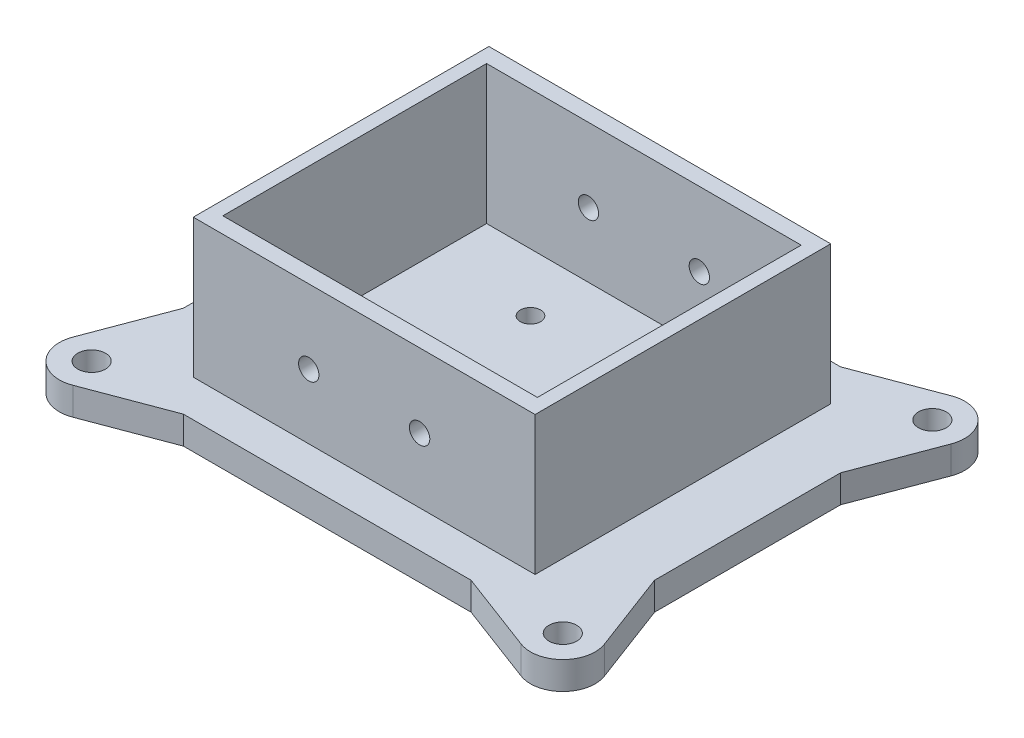
SolidWorks part; units mm, degrees
ref_plane "前视基准面" through (0, 0, 0) normal (0, 0, 1) x (1, 0, 0)
ref_plane "上视基准面" through (0, 0, 0) normal (0, 1, 0) x (1, 0, 0)
ref_plane "右视基准面" through (0, 0, 0) normal (1, 0, 0) x (0, 0, -1)
other "Configuration Table"
sketch "Sketch1" plane through (0, 0, 0) normal (0, 1, 0) x (1, 0, 0)
  line L0 (-24.2665, 23.2754) -> (-15.5689, 20)
  line L10 (24.2665, 23.2754) -> (15.5689, 20)
  line L11 (24.2665, -23.2754) -> (15.5689, -20)
  line L12 (-24.2665, -23.2754) -> (-15.5689, -20)
  line L13 (-28.7754, 18.7665) -> (-25.5, 10.0689)
  line L14 (28.7754, 18.7665) -> (25.5, 10.0689)
  line L15 (28.7754, -18.7665) -> (25.5, -10.0689)
  line L16 (-28.7754, -18.7665) -> (-25.5, -10.0689)
  line L17 (-25.5, 10.0689) -> (-25.5, -10.0689)
  line L18 (-15.5689, 20) -> (15.5689, 20)
  line L20 (25.5, 10.0689) -> (25.5, -10.0689)
  line L24 (-15.5689, -20) -> (15.5689, -20)
  circle A0 centre (-25.5, 20) radius 1.5
  circle A1 centre (25.5, 20) radius 1.5
  circle A2 centre (25.5, -20) radius 1.5
  circle A3 centre (-25.5, -20) radius 1.5
  arc A4 (-24.2665, 23.2754) -> (-28.7754, 18.7665) centre (-25.5, 20) ccw
  arc A5 (28.7754, 18.7665) -> (24.2665, 23.2754) centre (25.5, 20) ccw
  arc A6 (24.2665, -23.2754) -> (28.7754, -18.7665) centre (25.5, -20) ccw
  arc A7 (-28.7754, -18.7665) -> (-24.2665, -23.2754) centre (-25.5, -20) ccw
  point P0 (0, 0)
  dimension "D1" = 40
  dimension "D2" = 51
extrude "Boss-Extrude2" add sketch "Sketch1" along normal blind 3
sketch "Sketch2" plane through (0, 3, 0) normal (0, 1, 0) x (1, 0, 0)
  line L1 (-17.025, 14.275) -> (17.025, 14.275)
  line L2 (-17.025, 14.275) -> (-17.025, -14.275)
  line L3 (-17.025, -14.275) -> (17.025, -14.275)
  line L4 (17.025, 14.275) -> (17.025, -14.275)
  line L5 (0, -14.275) -> (0, 14.275) construction
  line L6 (-17.025, 0) -> (17.025, 0) construction
  line L7 (-18.5, 16) -> (18.5, 16)
  line L8 (-18.5, 16) -> (-18.5, -16)
  line L9 (-18.5, -16) -> (18.5, -16)
  line L10 (18.5, 16) -> (18.5, -16)
  line L11 (0, -16) -> (0, 16) construction
  line L12 (-18.5, 0) -> (18.5, 0) construction
  line L13 (-6, 8) -> (6, 8)
  line L14 (-6, 8) -> (-6, -8)
  line L15 (-6, -8) -> (6, -8)
  line L16 (6, 8) -> (6, -8)
  line L17 (0, -8) -> (0, 8) construction
  line L18 (-6, 0) -> (6, 0) construction
  circle A0 centre (-6, 8) radius 1.1
  circle A1 centre (6, 8) radius 1.1
  circle A2 centre (6, -8) radius 1.1
  circle A3 centre (-6, -8) radius 1.1
  point P0 (0, 0)
  point P4 (0, 0)
  point P11 (0, 0)
  dimension "D1" = 28.55
  dimension "D2" = 34.05
  dimension "D3" = 32
  dimension "D4" = 37
  dimension "D5" = 16
  dimension "D6" = 12
extrude "Boss-Extrude3" add sketch "Sketch2" along normal blind 15 contours L10 L7 L8 L9 L1 L4 L3 L2 region at (0, 3, -15.5108)
sketch "Sketch3" plane through (0, 0, -14.275) normal (0, 0, 1) x (1, 0, 0)
  line L0 (-17.025, 3) -> (17.025, 3) construction
  line L1 (-6, -4) -> (6, -4)
  line L2 (-6, -4) -> (-6, 10)
  line L3 (-6, 10) -> (6, 10)
  line L4 (6, -4) -> (6, 10)
  line L5 (0, 10) -> (0, -4) construction
  line L6 (-6, 3) -> (6, 3) construction
  circle A0 centre (-6, 10) radius 1.1
  circle A1 centre (6, 10) radius 1.1
  point P0 (0, 3)
  dimension "D1" = 14
  dimension "D2" = 12
extrude "Cut-Extrude1" cut sketch "Sketch3" against normal blind 11 and the other way blind 40 contours L3 A0 L2 | L2 A0 L3 | L4 A1 L3 | L3 A1 L4 region at (-6.1556, 10.1556, -14.275) region at (-5.5331, 9.5331, -14.275) region at (5.5331, 9.5331, -14.275) region at (6.1556, 10.1556, -14.275)
extrude "Cut-Extrude2" cut sketch "Sketch2<4>" against normal blind 11 contours A0 | A1 | A2 | A3
sketch "Sketch2<4>" plane through (0, 3, 0) normal (0, 1, 0) x (1, 0, 0) same geometry as "Sketch2"
sketch "Sketch4" plane through (0, 0, 0) normal (0, -1, 0) x (1, 0, 0)
  circle A0 centre (6, 8) radius 2
  circle A1 centre (6, -8) radius 2
  circle A2 centre (-6, -8) radius 2
  circle A3 centre (-6, 8) radius 2
extrude "Cut-Extrude3" [suppressed] cut sketch "Sketch4" against normal blind 2
